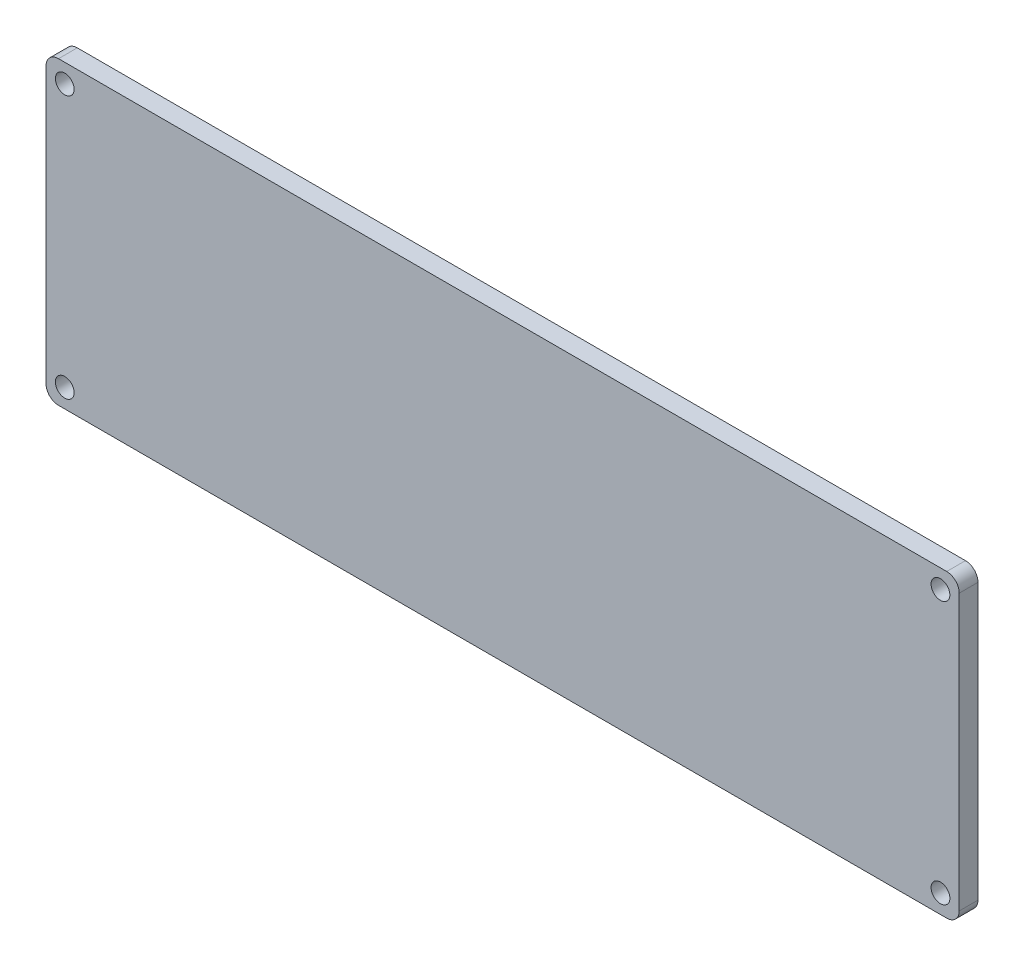
SolidWorks part; units mm, degrees
material "Perspex (TM) GS Acrylic Cast Sheet"
ref_plane "Front Plane" through (0, 0, 0) normal (0, 0, 1) x (1, 0, 0)
ref_plane "Top Plane" through (0, 0, 0) normal (0, 1, 0) x (1, 0, 0)
ref_plane "Right Plane" through (0, 0, 0) normal (1, 0, 0) x (0, 0, -1)
sketch "Sketch1" plane through (0, 0, 0) normal (0, 0, 1) x (1, 0, 0)
  line L0 (3, 45) -> (143, 45)
  line L1 (0, 0) -> (146, 0)
  line L2 (0, 0) -> (0, 48)
  line L3 (0, 48) -> (146, 48)
  line L4 (146, 0) -> (146, 48)
  line L5 (143, 3) -> (143, 45)
  line L6 (3, 3) -> (143, 3)
  line L7 (3, 3) -> (3, 45)
  circle A0 centre (3, 45) radius 1.5
  circle A1 centre (3, 3) radius 1.5
  circle A2 centre (143, 45) radius 1.5
  circle A3 centre (143, 3) radius 1.5
  dimension "D4" = 3
  dimension "D1" = 146
  dimension "D2" = 48
  dimension "D3" = 3
extrude "Boss-Extrude1" add sketch "Sketch1" along normal blind 3 contours L1 L4 L3 L2 A3 L6 A1 L7 A0 L0 A2 L5 | A3 L5 A2 L0 A0 L7 A1 L6 region at (73, 24, 0) region at (1.5369, 24, 0)
fillet "Fillet1" radius 2 4 edges at (0, 0, 1.5) (146, 0, 1.5) (146, 48, 1.5) (0, 48, 1.5)
